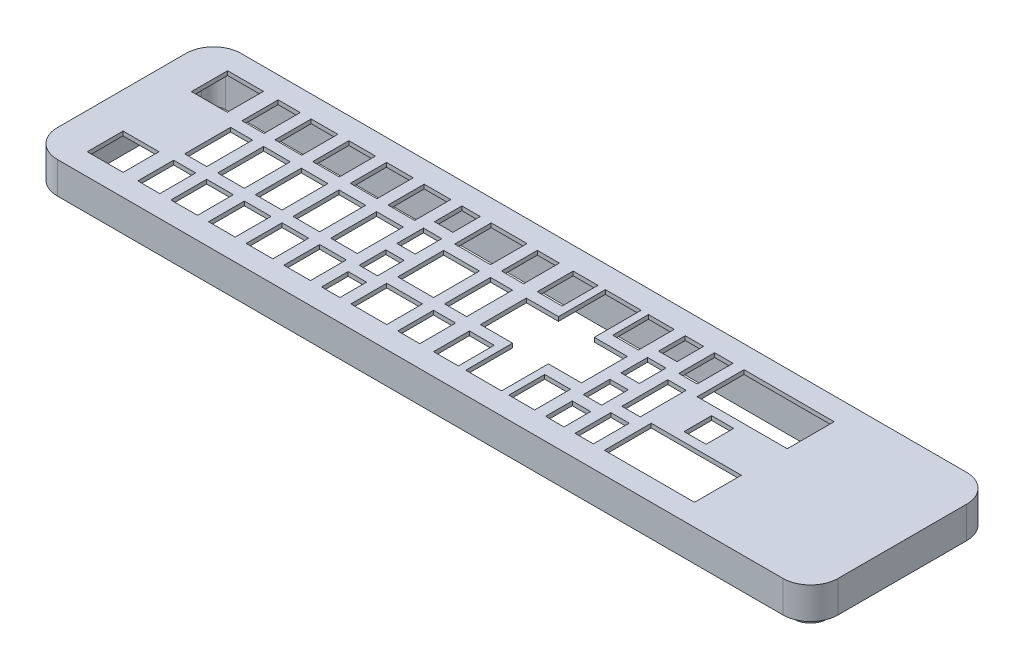
SolidWorks part; units mm, degrees
material "PVB"
ref_plane "Front Plane" through (0, 0, 0) normal (0, 0, 1) x (1, 0, 0)
ref_plane "Top Plane" through (0, 0, 0) normal (0, 1, 0) x (1, 0, 0)
ref_plane "Right Plane" through (0, 0, 0) normal (1, 0, 0) x (0, 0, -1)
ref_axis "X-axis" through (-88.99, 0, 0) along (1, 0, 0)
ref_axis "Y-axis" through (0, 55, 0) along (0, -1, 0)
ref_axis "Z-axis" through (0, 0, -88.99) along (0, 0, 1)
sketch "Sketch1" plane through (0, 0, 0) normal (0, 1, 0) x (1, 0, 0)
  line L1 (107.95, 25.4) -> (-107.95, 25.4)
  line L2 (107.95, 25.4) -> (107.95, -25.4)
  line L3 (107.95, -25.4) -> (-107.95, -25.4)
  line L4 (-107.95, 25.4) -> (-107.95, -25.4)
  line L5 (107.95, 25.4) -> (-107.95, -25.4) construction
  line L6 (107.95, -25.4) -> (-107.95, 25.4) construction
  point P0 (0, 0)
  dimension "D1" = 215.9
  dimension "D2" = 50.8
extrude "Boss-Extrude1" add sketch "Sketch1" along normal blind 8.763
sketch "Sketch4" plane through (0, 8.763, 0) normal (0, 1, 0) x (1, 0, 0)
  line L0 (-98.044, 19.4056) -> (-98.044, 9.398)
  line L1 (-6.096, 6.2484) -> (-6.096, -6.4516)
  line L2 (-12.192, 19.2024) -> (-12.192, 9.2964)
  line L3 (-2.286, 6.2484) -> (4.572, 6.2484)
  line L4 (-88.138, 19.4056) -> (-88.138, 9.398)
  line L5 (-84.074, 19.4056) -> (-84.074, 9.398)
  line L6 (-77.978, 19.4056) -> (-77.978, 9.398)
  line L7 (-74.93, 19.4056) -> (-74.93, 9.398)
  line L8 (-67.564, 19.4056) -> (-67.564, 9.398)
  line L9 (-64.516, 19.4056) -> (-64.516, 9.398)
  line L10 (-57.15, 19.4056) -> (-57.15, 9.398)
  line L11 (-54.102, 19.4056) -> (-54.102, 9.398)
  line L12 (-46.736, 19.4056) -> (-46.736, 9.398)
  line L13 (-43.688, 19.4056) -> (-43.688, 9.398)
  line L14 (-36.322, 19.4056) -> (-36.322, 9.398)
  line L15 (-33.274, 19.4056) -> (-33.274, 11.8364)
  line L16 (36.83, 19.2024) -> (36.83, 9.2964)
  line L17 (33.782, 19.2024) -> (33.782, 11.8364)
  line L18 (28.702, 19.2024) -> (28.702, 11.8364)
  line L19 (25.654, 19.2024) -> (25.654, 9.2964)
  line L20 (18.542, 19.2024) -> (18.542, 9.2964)
  line L21 (16.51, 19.2024) -> (16.51, 8.89)
  line L22 (6.604, 19.2024) -> (6.604, 8.89)
  line L23 (-28.194, 19.4056) -> (-28.194, 11.8364)
  line L25 (-25.146, 9.2964) -> (-15.24, 9.2964)
  line L26 (-12.192, 6.2484) -> (-12.192, -6.4516)
  line L27 (-6.096, 19.2024) -> (-6.096, 9.2964)
  line L28 (-2.286, 19.2024) -> (-2.286, 9.2964)
  line L29 (4.572, 19.2024) -> (4.572, 9.2964)
  line L30 (-98.044, 19.4056) -> (-88.138, 19.4056)
  line L31 (-98.044, -19.4056) -> (-88.138, -19.4056)
  line L32 (-98.044, -9.4996) -> (-88.138, -9.4996)
  line L33 (-98.044, 9.398) -> (-88.138, 9.398)
  line L34 (-33.274, 8.7884) -> (-28.194, 8.7884)
  line L35 (-33.274, -8.9916) -> (-28.194, -8.9916)
  line L36 (-84.074, -19.4056) -> (-77.978, -19.4056)
  line L37 (-84.074, -9.4996) -> (-77.978, -9.4996)
  line L38 (-84.074, -6.4516) -> (-77.978, -6.4516)
  line L39 (-84.074, 9.398) -> (-77.978, 9.398)
  line L40 (-84.074, 6.2484) -> (-77.978, 6.2484)
  line L41 (-84.074, 19.4056) -> (-77.978, 19.4056)
  line L42 (-43.688, -19.4056) -> (-36.322, -19.4056)
  line L43 (-43.688, -9.4996) -> (-36.322, -9.4996)
  line L44 (-43.688, -6.4516) -> (-36.322, -6.4516)
  line L45 (-43.688, 6.2484) -> (-36.322, 6.2484)
  line L46 (-43.688, 9.398) -> (-36.322, 9.398)
  line L47 (-54.102, -19.4056) -> (-46.736, -19.4056)
  line L48 (-54.102, -9.4996) -> (-46.736, -9.4996)
  line L49 (-54.102, -6.4516) -> (-46.736, -6.4516)
  line L50 (-54.102, 6.2484) -> (-46.736, 6.2484)
  line L51 (-54.102, 9.398) -> (-46.736, 9.398)
  line L52 (-64.516, -19.4056) -> (-57.15, -19.4056)
  line L53 (-64.516, -9.4996) -> (-57.15, -9.4996)
  line L54 (-64.516, -6.4516) -> (-57.15, -6.4516)
  line L55 (-64.516, 6.2484) -> (-57.15, 6.2484)
  line L56 (-64.516, 9.398) -> (-57.15, 9.398)
  line L57 (-74.93, -19.4056) -> (-67.564, -19.4056)
  line L58 (-74.93, -9.4996) -> (-67.564, -9.4996)
  line L59 (-74.93, -6.4516) -> (-67.564, -6.4516)
  line L60 (-74.93, 6.2484) -> (-67.564, 6.2484)
  line L61 (-74.93, 9.398) -> (-67.564, 9.398)
  line L62 (-74.93, 19.4056) -> (-67.564, 19.4056)
  line L63 (-64.516, 19.4056) -> (-57.15, 19.4056)
  line L64 (-54.102, 19.4056) -> (-46.736, 19.4056)
  line L65 (-43.688, 19.4056) -> (-36.322, 19.4056)
  line L66 (-98.044, -9.4996) -> (-98.044, -19.4056)
  line L67 (-88.138, -9.4996) -> (-88.138, -19.4056)
  line L68 (-33.274, 11.8364) -> (-28.194, 11.8364)
  line L69 (-33.274, -1.6256) -> (-28.194, -1.6256)
  line L70 (-33.274, 1.4224) -> (-28.194, 1.4224)
  line L71 (-33.274, -12.0396) -> (-28.194, -12.0396)
  line L72 (-33.274, 19.4056) -> (-28.194, 19.4056)
  line L73 (-33.274, -19.4056) -> (-28.194, -19.4056)
  line L74 (-84.074, -9.4996) -> (-84.074, -19.4056)
  line L75 (-77.978, -9.4996) -> (-77.978, -19.4056)
  line L76 (-74.93, -9.4996) -> (-74.93, -19.4056)
  line L77 (-67.564, -9.4996) -> (-67.564, -19.4056)
  line L78 (-64.516, -9.4996) -> (-64.516, -19.4056)
  line L79 (-57.15, -9.4996) -> (-57.15, -19.4056)
  line L80 (-54.102, -9.4996) -> (-54.102, -19.4056)
  line L81 (-46.736, -9.4996) -> (-46.736, -19.4056)
  line L82 (-43.688, -9.4996) -> (-43.688, -19.4056)
  line L83 (-36.322, -9.4996) -> (-36.322, -19.4056)
  line L84 (-36.322, 6.2484) -> (-36.322, -6.4516)
  line L85 (-43.688, 6.2484) -> (-43.688, -6.4516)
  line L86 (-46.736, 6.2484) -> (-46.736, -6.4516)
  line L87 (-54.102, 6.2484) -> (-54.102, -6.4516)
  line L88 (-57.15, 6.2484) -> (-57.15, -6.4516)
  line L89 (-64.516, 6.2484) -> (-64.516, -6.4516)
  line L90 (-67.564, 6.2484) -> (-67.564, -6.4516)
  line L91 (-74.93, 6.2484) -> (-74.93, -6.4516)
  line L92 (-77.978, 6.2484) -> (-77.978, -6.4516)
  line L93 (-84.074, 6.2484) -> (-84.074, -6.4516)
  line L94 (-33.274, -12.0396) -> (-33.274, -19.4056)
  line L95 (-28.194, -12.0396) -> (-28.194, -19.4056)
  line L96 (-28.194, -1.6256) -> (-28.194, -8.9916)
  line L97 (-33.274, -1.6256) -> (-33.274, -8.9916)
  line L98 (-33.274, 8.7884) -> (-33.274, 1.4224)
  line L99 (-28.194, 8.7884) -> (-28.194, 1.4224)
  line L100 (-25.146, -19.4056) -> (-15.24, -19.4056)
  line L101 (-25.146, -9.4996) -> (-15.24, -9.4996)
  line L102 (-25.146, -6.4516) -> (-15.24, -6.4516)
  line L103 (-25.146, 6.2484) -> (-15.24, 6.2484)
  line L106 (-25.146, -9.4996) -> (-25.146, -19.4056)
  line L107 (-15.24, -9.4996) -> (-15.24, -19.4056)
  line L108 (-25.146, 6.2484) -> (-25.146, -6.4516)
  line L109 (-12.192, 19.2024) -> (-6.096, 19.2024)
  line L111 (-6.096, 9.2964) -> (-12.192, 9.2964)
  line L113 (-12.192, 6.2484) -> (-6.096, 6.2484)
  line L115 (-6.096, -6.4516) -> (-12.192, -6.4516)
  line L117 (-15.24, 6.2484) -> (-15.24, -6.4516)
  line L119 (-12.192, -9.4996) -> (-6.096, -9.4996)
  line L120 (-6.096, -9.4996) -> (-6.096, -19.4056)
  line L121 (-6.096, -19.4056) -> (-12.192, -19.4056)
  line L122 (-12.192, -19.4056) -> (-12.192, -9.4996)
  line L123 (-2.286, -19.4056) -> (4.572, -19.4056)
  line L124 (4.572, -19.4056) -> (4.572, -9.4996)
  line L125 (4.572, -9.4996) -> (-2.286, -9.4996)
  line L126 (-2.286, -9.4996) -> (-2.286, -19.4056)
  line L127 (-2.286, 9.2964) -> (4.572, 9.2964)
  line L129 (4.572, 19.2024) -> (-2.286, 19.2024)
  line L134 (6.604, -19.4056) -> (16.51, -19.4056)
  line L136 (18.796, -6.4516) -> (25.654, -6.4516)
  line L137 (25.654, -6.4516) -> (25.654, 6.2484)
  line L138 (25.654, 6.2484) -> (18.796, 6.2484)
  line L140 (16.51, 19.2024) -> (6.604, 19.2024)
  line L143 (6.604, -19.4056) -> (6.604, -8.89)
  line L145 (18.542, -19.4056) -> (25.654, -19.4056)
  line L146 (25.654, -19.4056) -> (25.654, -9.4996)
  line L147 (25.654, -9.4996) -> (18.542, -9.4996)
  line L148 (18.542, -9.4996) -> (18.542, -19.4056)
  line L149 (18.542, 9.2964) -> (25.654, 9.2964)
  line L151 (25.654, 19.2024) -> (18.542, 19.2024)
  line L153 (41.91, 19.2024) -> (41.91, 9.2964)
  line L154 (44.958, 19.2024) -> (44.958, 6.2484)
  line L155 (36.83, -19.4056) -> (41.91, -19.4056)
  line L156 (41.91, -19.4056) -> (41.91, -9.4996)
  line L157 (41.91, -9.4996) -> (36.83, -9.4996)
  line L158 (36.83, -9.4996) -> (36.83, -19.4056)
  line L159 (36.83, -6.4516) -> (41.91, -6.4516)
  line L160 (41.91, -6.4516) -> (41.91, 6.2484)
  line L161 (41.91, 6.2484) -> (36.83, 6.2484)
  line L162 (36.83, 6.2484) -> (36.83, -6.4516)
  line L163 (36.83, 19.2024) -> (41.91, 19.2024)
  line L165 (41.91, 9.2964) -> (36.83, 9.2964)
  line L167 (28.702, -12.0396) -> (33.782, -12.0396)
  line L168 (33.782, -12.0396) -> (33.782, -19.4056)
  line L169 (33.782, -19.4056) -> (28.702, -19.4056)
  line L170 (28.702, -19.4056) -> (28.702, -12.0396)
  line L171 (28.702, -8.9916) -> (33.782, -8.9916)
  line L172 (33.782, -8.9916) -> (33.782, -1.6256)
  line L173 (33.782, -1.6256) -> (28.702, -1.6256)
  line L174 (28.702, -1.6256) -> (28.702, -8.9916)
  line L175 (28.702, 1.4224) -> (33.782, 1.4224)
  line L176 (33.782, 1.4224) -> (33.782, 8.7884)
  line L177 (33.782, 8.7884) -> (28.702, 8.7884)
  line L178 (28.702, 8.7884) -> (28.702, 1.4224)
  line L179 (28.702, 11.8364) -> (33.782, 11.8364)
  line L181 (33.782, 19.2024) -> (28.702, 19.2024)
  line L184 (-2.286, 6.2484) -> (-2.286, -6.4516)
  line L185 (-25.146, 9.2964) -> (-25.146, 19.4056)
  line L186 (-25.146, 19.4056) -> (-15.24, 19.4056)
  line L187 (-15.24, 9.2964) -> (-15.24, 19.4056)
  line L188 (6.604, -8.89) -> (6.604, -6.4516)
  line L191 (4.572, 6.2484) -> (6.604, 6.2484)
  line L192 (6.604, 6.2484) -> (6.604, 8.89)
  line L193 (16.51, -19.4056) -> (16.51, -6.4516)
  line L194 (16.51, -6.4516) -> (18.796, -6.4516)
  line L195 (16.51, 8.89) -> (16.51, 6.2484)
  line L196 (16.51, 6.2484) -> (18.796, 6.2484)
  line L197 (4.572, -6.4516) -> (6.604, -6.4516)
  line L203 (44.958, -19.4056) -> (69.8754, -19.4056)
  line L204 (107.95, 25.4) -> (-107.95, 25.4) construction
  line L205 (44.958, 19.2024) -> (69.8754, 19.2024)
  line L206 (69.8754, 6.2484) -> (44.958, 6.2484)
  line L207 (44.958, -6.4516) -> (69.8754, -6.4516)
  line L208 (51.4858, -3.9116) -> (57.5818, -3.9116)
  line L209 (51.4858, 3.7084) -> (57.5818, 3.7084)
  line L212 (69.8754, 19.2024) -> (69.8754, 6.2484)
  line L214 (-2.286, -6.4516) -> (4.572, -6.4516)
  line L215 (57.5818, 3.7084) -> (57.5818, -3.9116)
  line L216 (51.4858, 3.7084) -> (51.4858, -3.9116)
  line L217 (44.958, -6.4516) -> (44.958, -19.4056)
  line L220 (69.8754, -6.4516) -> (69.8754, -19.4056)
  dimension "D16" = 5.9944
  dimension "D17" = 6.858
  dimension "D19" = 6.858
  dimension "D1" = 7.366
  dimension "D4" = 6.096
  dimension "D5" = 3.048
  dimension "D6" = 7.366
  dimension "D7" = 7.366
  dimension "D8" = 7.5692
  dimension "D9" = 3.048
  dimension "D10" = 3.048
  dimension "D11" = 3.048
  dimension "D12" = 7.366
  dimension "D13" = 7.366
  dimension "D14" = 5.9944
  dimension "D15" = 2.54
  dimension "D18" = 12.7
  dimension "D20" = 9.906
  dimension "D21" = 6.858
  dimension "D22" = 3.048
  dimension "D23" = 3.048
  dimension "D24" = 3.048
  dimension "D25" = 3.048
  dimension "D26" = 9.906
  dimension "D27" = 3.048
  dimension "D28" = 2.54
  dimension "D29" = 3.048
  dimension "D30" = 3.048
  dimension "D31" = 9.906
  dimension "D32" = 9.906
  dimension "D33" = 2.032
  dimension "D34" = 7.112
  dimension "D35" = 3.048
  dimension "D36" = 5.08
  dimension "D38" = 3.048
  dimension "D39" = 5.08
  dimension "D42" = 12.954
  dimension "D43" = 12.954
  dimension "D46" = 24.9174
fillet "Fillet9" radius 7.62 4 edges at (-107.95, 4.3815, -25.4) (-107.95, 4.3815, 25.4) (107.95, 4.3815, 25.4) (107.95, 4.3815, -25.4)
sketch "Sketch22" plane through (0, 0, 0) normal (0, -1, 0) x (1, 0, 0)
  line L24 (106.172, -17.78) -> (106.172, 17.78)
  line L25 (-100.33, -23.622) -> (100.33, -23.622)
  line L26 (-106.172, 17.78) -> (-106.172, -17.78)
  line L27 (100.33, 23.622) -> (-100.33, 23.622)
  line L28 (106.172, -17.78) -> (106.172, 17.78)
  line L29 (-100.33, -23.622) -> (100.33, -23.622)
  line L30 (-106.172, 17.78) -> (-106.172, -17.78)
  line L31 (100.33, 23.622) -> (-100.33, 23.622)
  arc A20 (106.172, 17.78) -> (100.33, 23.622) centre (100.33, 17.78) ccw
  arc A21 (100.33, -23.622) -> (106.172, -17.78) centre (100.33, -17.78) ccw
  arc A22 (-106.172, -17.78) -> (-100.33, -23.622) centre (-100.33, -17.78) ccw
  arc A23 (-100.33, 23.622) -> (-106.172, 17.78) centre (-100.33, 17.78) ccw
  arc A24 (106.172, 17.78) -> (100.33, 23.622) centre (100.33, 17.78) ccw
  arc A25 (100.33, -23.622) -> (106.172, -17.78) centre (100.33, -17.78) ccw
  arc A26 (-106.172, -17.78) -> (-100.33, -23.622) centre (-100.33, -17.78) ccw
  arc A27 (-100.33, 23.622) -> (-106.172, 17.78) centre (-100.33, 17.78) ccw
  dimension "D1" = 1.778
extrude "Cut-Extrude2" cut sketch "Sketch22" against normal blind 7.62
sketch "Sketch23" plane through (0, 7.62, 0) normal (0, -1, 0) x (1, 0, 0)
  line L5 (-103.632, 17.78) -> (-103.632, -17.78)
  line L6 (-100.33, -21.082) -> (100.33, -21.082)
  line L7 (103.632, -17.78) -> (103.632, 17.78)
  line L8 (100.33, 22.352) -> (-100.33, 22.352)
  line L9 (-104.902, 17.78) -> (-104.902, -17.78)
  line L10 (-100.33, -22.352) -> (100.33, -22.352)
  line L11 (104.902, -17.78) -> (104.902, 17.78)
  line L12 (100.33, 22.352) -> (-100.33, 22.352)
  line L13 (-104.902, 17.78) -> (-104.902, -17.78)
  line L14 (-100.33, -22.352) -> (100.33, -22.352)
  line L15 (104.902, -17.78) -> (104.902, 17.78)
  line L16 (100.33, 21.082) -> (-100.33, 21.082)
  arc A4 (-100.33, 21.082) -> (-103.632, 17.78) centre (-100.33, 17.78) ccw
  arc A5 (-103.632, -17.78) -> (-100.33, -21.082) centre (-100.33, -17.78) ccw
  arc A6 (100.33, -21.082) -> (103.632, -17.78) centre (100.33, -17.78) ccw
  arc A7 (103.632, 17.78) -> (100.33, 21.082) centre (100.33, 17.78) ccw
  arc A8 (104.902, 17.78) -> (100.33, 22.352) centre (100.33, 17.78) ccw
  arc A9 (-100.33, 22.352) -> (-104.902, 17.78) centre (-100.33, 17.78) ccw
  arc A10 (-104.902, -17.78) -> (-100.33, -22.352) centre (-100.33, -17.78) ccw
  arc A11 (100.33, -22.352) -> (104.902, -17.78) centre (100.33, -17.78) ccw
  arc A12 (104.902, 17.78) -> (100.33, 22.352) centre (100.33, 17.78) ccw
  arc A13 (-100.33, 22.352) -> (-104.902, 17.78) centre (-100.33, 17.78) ccw
  arc A14 (-104.902, -17.78) -> (-100.33, -22.352) centre (-100.33, -17.78) ccw
  arc A15 (100.33, -22.352) -> (104.902, -17.78) centre (100.33, -17.78) ccw
  dimension "D1" = 1.27
  dimension "D2" = 1.27
extrude "Boss-Extrude2" add sketch "Sketch23" along normal blind 10.16
extrude "Cut-Extrude3" cut sketch "Sketch4" against normal through all
